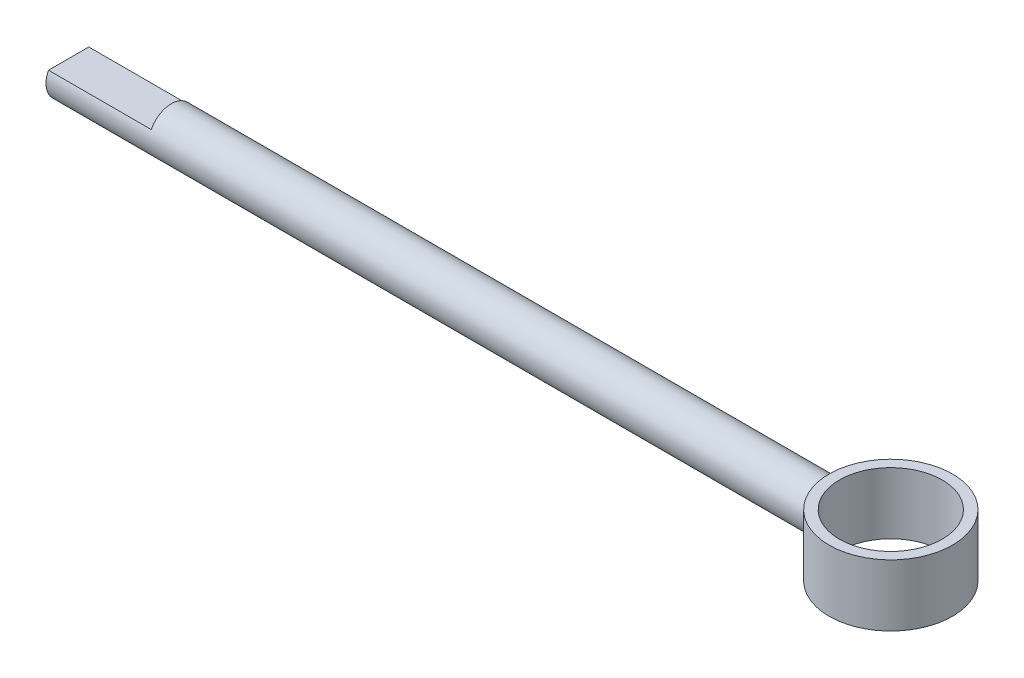
SolidWorks part; units mm, degrees
ref_plane "Front Plane" through (0, 0, 0) normal (0, 0, 1) x (1, 0, 0)
ref_plane "Top Plane" through (0, 0, 0) normal (0, 1, 0) x (1, 0, 0)
ref_plane "Right Plane" through (0, 0, 0) normal (1, 0, 0) x (0, 0, -1)
other "Configuration Table"
sketch "Sketch1" plane through (0, 0, 0) normal (0, 1, 0) x (1, 0, 0)
  line L1 (0, 0) -> (400, 0)
  line L2 (0, 0) -> (0, 11)
  line L3 (0, 11) -> (400, 11)
  line L4 (400, 0) -> (400, 11)
  circle A0 centre (400, 0) radius 30
revolve "Revolve1" add sketch "Sketch1" angle 360 about L1 region at (185.3438, 0, -5.5051)
extrude "Boss-Extrude1" add sketch "Sketch1<3>" along normal blind 15 and the other way blind 15 contours L1 A0 L3 L4 | L3 A0 L1 L4 region at (385.3367, 0, -5.4351) region at (401.8875, 0, 0.6996)
sketch "Sketch1<3>" plane through (0, 0, 0) normal (0, 1, 0) x (1, 0, 0) same geometry as "Sketch1"
sketch "Sketch2" plane through (0, 15, 0) normal (0, 1, 0) x (1, 0, 0)
  circle A0 centre (400, 0) radius 25
extrude "Cut-Extrude1" cut sketch "Sketch2" against normal blind 30
sketch "Sketch3" plane through (0, 0, 0) normal (-1, 0, 0) x (0, 0, 1)
  line L0 (0, 0) -> (0, 5)
  line L1 (0, 5) -> (-9.798, 5)
  line L2 (-9.798, 5) -> (9.798, 5)
  circle A0 centre (0, 0) radius 11 construction
  circle M2 centre (0, 0) radius 11
extrude "Cut-Extrude2" cut sketch "Sketch3" against normal blind 50 contours L1 L2 M2 region at (0, 7.4668, 0)
